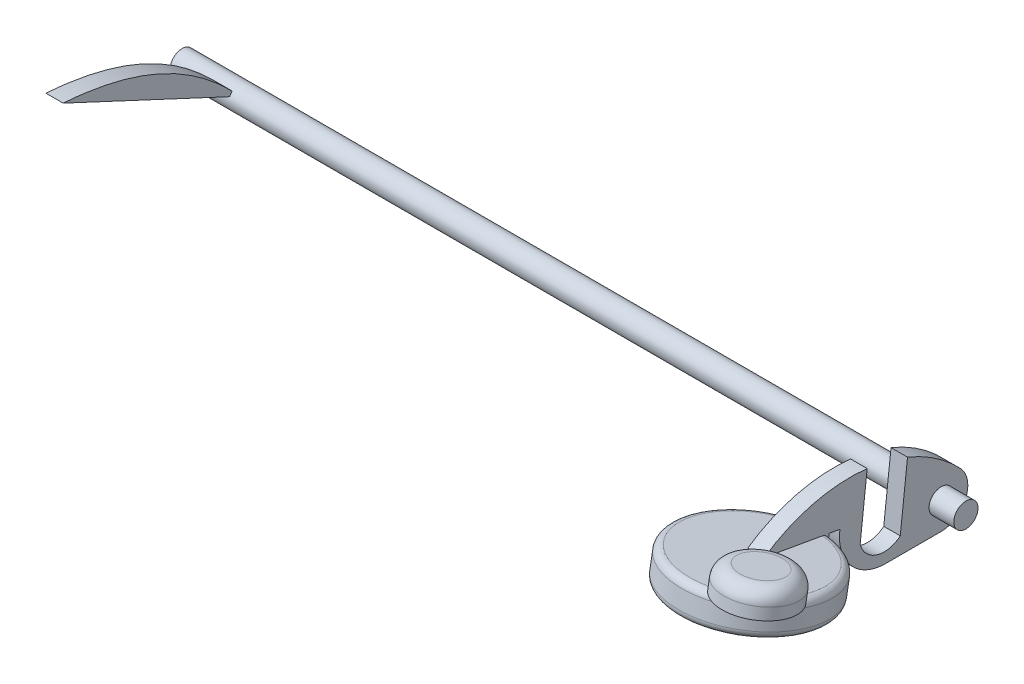
SolidWorks part; units mm, degrees
material "6061 Alloy"
ref_plane "Front Plane" through (0, 0, 0) normal (0, 0, 1) x (1, 0, 0)
ref_plane "Top Plane" through (0, 0, 0) normal (0, 1, 0) x (1, 0, 0)
ref_plane "Right Plane" through (0, 0, 0) normal (1, 0, 0) x (0, 0, -1)
sketch "Sketch1" plane through (0, 0, 0) normal (1, 0, 0) x (0, 0, -1)
  circle A0 centre (0, 0) radius 2.2352
  dimension "D1" = 4.4704
extrude "Boss-Extrude1" add sketch "Sketch1" along normal blind 144.7292
ref_plane "Plane1" through (137.1092, 0, 0) normal (1, 0, 0) x (0, 0, -1)
sketch "Sketch2" plane through (137.1092, 0, 0) normal (1, 0, 0) x (0, 0, -1)
  line L0 (2.4587, 0) -> (-2.4587, 0) construction
  line L1 (-18.6944, 4.7752) -> (-32.6523, 7.2364)
  line L2 (0, -4.9276) -> (-10.2636, -4.9276)
  line L3 (-13.6602, 11.9768) -> (-14.9538, 0.4829)
  line L4 (-6.2061, 10.0756) -> (-7.5473, -1.8415)
  arc A0 (0, -4.9276) -> (3.803, 3.1334) centre (0, 0) ccw
  arc A1 (-10.2636, -4.9276) -> (-18.6944, 4.7752) centre (-10.2636, 3.5865) cw
  arc A2 (-32.6523, 7.2364) -> (-13.6602, 11.9768) centre (-16.7952, -15.8783) cw
  arc A3 (-14.9538, 0.4829) -> (-7.5473, -1.8415) centre (-10.5143, 1.6668) ccw
  arc A4 (-13.6602, 11.9768) -> (-6.2061, 10.0756) centre (-16.7952, -15.8783) cw construction
  arc A5 (-6.2061, 10.0756) -> (3.803, 3.1334) centre (-16.7952, -15.8783) cw
  arc A6 (3.803, 3.1334) -> (0, -4.9276) centre (0, 0) ccw construction
  circle A8 centre (0, 0) radius 4.9276 construction
  point P1 (3.803, 3.1977)
  point P16 (0, 0)
  point P18 (0, 0)
  point P19 (0, 0)
  point P20 (0, 0)
  point P21 (-7.5473, -1.8415)
  point P22 (0, 0)
  point P23 (0, 0)
  dimension "D2" = 14.1732
  dimension "D6" = 8.5141
  dimension "D7" = 28.0309
  dimension "D8" = 4.5947
  dimension "D3" = 18.6944
  dimension "D4" = 10
  dimension "D5" = 4.7752
extrude "Boss-Extrude3" add sketch "Sketch2" along normal blind 3.048 contours A2 L3 A3 L4 A5 A0 L2 A1 L1
sketch "Sketch3" plane through (0, 1.4343, -0.2529) normal (0, -0.9848, 0.1736) x (1, 0, 0)
  line L0 (138.6332, 19.2396) -> (138.6332, 33.4128) construction
  line L1 (140.1572, 19.2396) -> (137.1092, 19.2396) construction
  line L2 (140.1572, 33.4128) -> (137.1092, 33.4128) construction
  circle A0 centre (138.6332, 34.124) radius 12.9794
  point P8 (9.2964, 28.7182)
  point P9 (9.2964, 35.2186)
  dimension "D1" = 25.9588
  dimension "D2" = 14.8844
extrude "Boss-Extrude4" add sketch "Sketch3" along normal blind 5.715
fillet "Fillet1" radius 1.27 2 edges at (138.6332, -0.5222, 21.5629) (138.6332, 9.6137, 46.1349)
sketch "Sketch4" plane through (0, 1.4343, -0.2529) normal (0, 0.9848, -0.1736) x (1, 0, 0)
  line L0 (138.6332, -33.4128) -> (147.261, -42.0406) construction
  line L1 (140.1572, -33.4128) -> (137.1092, -33.4128) construction
  line L2 (140.1572, -33.4128) -> (140.1572, -15.5325) construction
  arc A0 (137.1092, -22.5142) -> (140.1572, -22.5142) centre (138.6332, -34.124) ccw construction
  circle A1 centre (147.261, -42.0406) radius 6.477
  dimension "D1" = 45
  dimension "D2" = 12.954
extrude "Boss-Extrude5" add sketch "Sketch4" along normal blind 4.5974
fillet "Fillet2" radius 2.54 1 edges at (147.261, 14.3868, 46.7292)
ref_plane "Plane2" through (7.62, 0, 0) normal (1, 0, 0) x (0, 0, -1)
sketch "Sketch6" plane through (7.62, 0, 0) normal (1, 0, 0) x (0, 0, -1)
  line L0 (0, 0) -> (-32.7578, 15.2752)
  line L1 (28.8503, 0) -> (-28.8503, 0) construction
  line L2 (-3.7102, 3.692) -> (-10.9539, 9.9935) construction
  line L3 (-24.5399, 14.7214) -> (-40.9757, 15.829) construction
  spline S0 degree 3 poles (-32.7578, 15.2752) (-22.5819, 14.5895) (-10.9404, 10.6237) (-2.1347, 2.2907) (0, 0) knots 0 0 0 0 0.746549 1 1 1 1
  point P6 (-4.2198, 4.1892)
  point P7 (0, 0)
  point P9 (0, 0)
  point P12 (0, 0)
  dimension "D1" = 25
  dimension "D2" = 36.1442
extrude "Boss-Extrude6" add sketch "Sketch6" along normal blind 3.175
